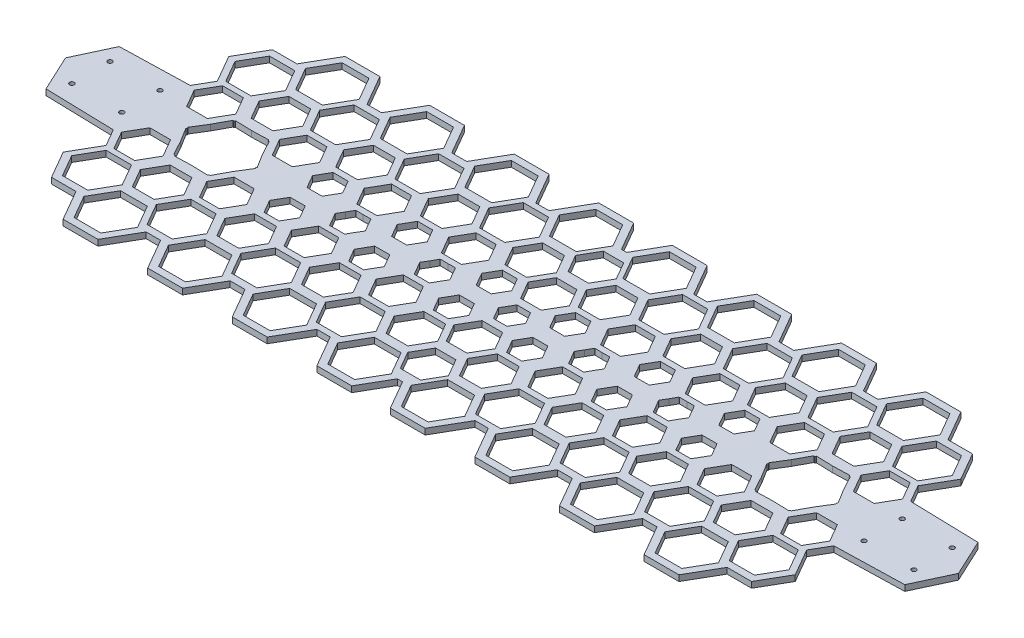
SolidWorks part; units mm, degrees
material "6061 Alloy"
ref_plane "Front Plane" through (0, 0, 0) normal (0, 0, 1) x (1, 0, 0)
ref_plane "Top Plane" through (0, 0, 0) normal (0, 1, 0) x (1, 0, 0)
ref_plane "Right Plane" through (0, 0, 0) normal (1, 0, 0) x (0, 0, -1)
sketch "Sketch2" plane through (0, 0, 0) normal (0, 1, 0) x (1, 0, 0)
  line L1 (-482.6, -152.4) -> (482.6, -152.4)
  line L2 (-482.6, -152.4) -> (-482.6, 152.4)
  line L3 (-482.6, 152.4) -> (482.6, 152.4)
  line L4 (482.6, -152.4) -> (482.6, 152.4)
  line L5 (-482.6, -152.4) -> (482.6, 152.4) construction
  line L6 (-482.6, 152.4) -> (482.6, -152.4) construction
  point P0 (0, 0)
  dimension "D1" = 304.8
  dimension "D2" = 965.2
extrude "Boss-Extrude1" add sketch "Sketch2" along normal blind 6.35
sketch "Sketch7" plane through (0, 6.35, 0) normal (0, 1, 0) x (1, 0, 0)
  line L166 (0, 0) -> (-401.7449, 0) construction
  line L215 (-31.5577, 37.3042) -> (-47.8332, 37.3042)
  line L216 (-47.8332, 37.3042) -> (-55.9709, 23.2093)
  line L217 (-55.9709, 23.2093) -> (-47.8332, 9.1144)
  line L218 (-47.8332, 9.1144) -> (-31.5577, 9.1144)
  line L219 (-31.5577, 9.1144) -> (-23.42, 23.2093)
  line L220 (-23.42, 23.2093) -> (-31.5577, 37.3042)
  line L221 (-16.1001, 64.2057) -> (-27.8978, 84.6399)
  line L222 (-27.8978, 84.6399) -> (-51.4931, 84.6399)
  line L223 (-51.4931, 84.6399) -> (-63.2908, 64.2057)
  line L224 (-63.2908, 64.2057) -> (-51.4931, 43.7716)
  line L225 (-51.4931, 43.7716) -> (-27.8978, 43.7716)
  line L226 (-27.8978, 43.7716) -> (-16.1001, 64.2057)
  line L227 (-10.6981, 119.7777) -> (-25.1968, 144.8901)
  line L228 (-25.1968, 144.8901) -> (-54.1941, 144.8901)
  line L229 (-54.1941, 144.8901) -> (-68.6928, 119.7777)
  line L230 (-68.6928, 119.7777) -> (-54.1941, 94.6652)
  line L231 (-54.1941, 94.6652) -> (-25.1968, 94.6652)
  line L232 (-25.1968, 94.6652) -> (-10.6981, 119.7777)
  line L233 (-64.4077, 39.3283) -> (-75.2304, 58.0738)
  line L234 (-75.2304, 58.0738) -> (-96.8759, 58.0738)
  line L235 (-96.8759, 58.0738) -> (-107.6986, 39.3283)
  line L236 (-107.6986, 39.3283) -> (-96.8759, 20.5828)
  line L237 (-96.8759, 20.5828) -> (-75.2304, 20.5828)
  line L238 (-75.2304, 20.5828) -> (-64.4077, 39.3283)
  line L239 (-58.7454, 88.2604) -> (-72.3993, 111.9096)
  line L240 (-72.3993, 111.9096) -> (-99.707, 111.9096)
  line L241 (-99.707, 111.9096) -> (-113.3609, 88.2604)
  line L242 (-113.3609, 88.2604) -> (-99.707, 64.6112)
  line L243 (-99.707, 64.6112) -> (-72.3993, 64.6112)
  line L244 (-72.3993, 64.6112) -> (-58.7454, 88.2604)
  line L245 (-122.9977, 37.3042) -> (-139.2732, 37.3042)
  line L246 (-67.2122, 0.2372) -> (-75.5284, 14.1669)
  line L247 (-75.5284, 14.1669) -> (-91.7499, 13.9297)
  line L248 (-91.7499, 13.9297) -> (-99.6553, -0.2372)
  line L249 (-99.6553, -0.2372) -> (-91.3391, -14.1669)
  line L250 (-91.3391, -14.1669) -> (-75.1176, -13.9297)
  line L251 (-75.1176, -13.9297) -> (-67.2122, 0.2372)
  line L252 (-139.2732, 37.3042) -> (-147.4109, 23.2093)
  line L253 (-147.4109, 23.2093) -> (-139.2732, 9.1144)
  line L254 (-139.2732, 9.1144) -> (-122.9977, 9.1144)
  line L255 (-122.9977, 9.1144) -> (-114.86, 23.2093)
  line L256 (-114.86, 23.2093) -> (-122.9977, 37.3042)
  line L257 (-107.5401, 64.2057) -> (-119.3378, 84.6399)
  line L258 (-119.3378, 84.6399) -> (-142.9331, 84.6399)
  line L259 (-142.9331, 84.6399) -> (-154.7308, 64.2057)
  line L260 (-154.7308, 64.2057) -> (-142.9331, 43.7716)
  line L261 (-142.9331, 43.7716) -> (-119.3378, 43.7716)
  line L262 (-119.3378, 43.7716) -> (-107.5401, 64.2057)
  line L263 (-102.1381, 119.7777) -> (-116.6368, 144.8901)
  line L264 (-116.6368, 144.8901) -> (-145.6341, 144.8901)
  line L265 (-145.6341, 144.8901) -> (-160.1328, 119.7777)
  line L266 (-160.1328, 119.7777) -> (-145.6341, 94.6652)
  line L267 (-145.6341, 94.6652) -> (-116.6368, 94.6652)
  line L268 (-116.6368, 94.6652) -> (-102.1381, 119.7777)
  line L269 (-155.8477, 39.3283) -> (-166.6704, 58.0738)
  line L270 (-166.6704, 58.0738) -> (-188.3159, 58.0738)
  line L271 (-188.3159, 58.0738) -> (-199.1386, 39.3283)
  line L272 (-199.1386, 39.3283) -> (-188.3159, 20.5828)
  line L273 (-188.3159, 20.5828) -> (-166.6704, 20.5828)
  line L274 (-166.6704, 20.5828) -> (-155.8477, 39.3283)
  line L275 (-150.1854, 88.2604) -> (-163.8393, 111.9096)
  line L276 (-163.8393, 111.9096) -> (-191.147, 111.9096)
  line L277 (-191.147, 111.9096) -> (-204.8009, 88.2604)
  line L278 (-204.8009, 88.2604) -> (-191.147, 64.6112)
  line L279 (-191.147, 64.6112) -> (-163.8393, 64.6112)
  line L280 (-163.8393, 64.6112) -> (-150.1854, 88.2604)
  line L281 (-158.6522, 0.2372) -> (-166.9684, 14.1669)
  line L282 (-166.9684, 14.1669) -> (-183.1899, 13.9297)
  line L283 (-183.1899, 13.9297) -> (-191.0953, -0.2372)
  line L284 (-191.0953, -0.2372) -> (-182.7791, -14.1669)
  line L285 (-182.7791, -14.1669) -> (-166.5576, -13.9297)
  line L286 (-166.5576, -13.9297) -> (-158.6522, 0.2372)
  line L287 (-214.4377, 37.3042) -> (-230.7132, 37.3042)
  line L288 (-230.7132, 37.3042) -> (-238.8509, 23.2093)
  line L289 (-238.8509, 23.2093) -> (-230.7132, 9.1144)
  line L290 (-230.7132, 9.1144) -> (-214.4377, 9.1144)
  line L291 (-214.4377, 9.1144) -> (-206.3, 23.2093)
  line L292 (-206.3, 23.2093) -> (-214.4377, 37.3042)
  line L293 (-198.9801, 64.2057) -> (-210.7778, 84.6399)
  line L294 (-210.7778, 84.6399) -> (-234.3731, 84.6399)
  line L295 (-234.3731, 84.6399) -> (-246.1708, 64.2057)
  line L296 (-246.1708, 64.2057) -> (-234.3731, 43.7716)
  line L297 (-234.3731, 43.7716) -> (-210.7778, 43.7716)
  line L298 (-210.7778, 43.7716) -> (-198.9801, 64.2057)
  line L299 (-193.5781, 119.7777) -> (-208.0768, 144.8901)
  line L300 (-208.0768, 144.8901) -> (-237.0741, 144.8901)
  line L301 (-237.0741, 144.8901) -> (-251.5728, 119.7777)
  line L302 (-251.5728, 119.7777) -> (-237.0741, 94.6652)
  line L303 (-237.0741, 94.6652) -> (-208.0768, 94.6652)
  line L304 (-208.0768, 94.6652) -> (-193.5781, 119.7777)
  line L305 (-247.2877, 39.3283) -> (-258.1104, 58.0738)
  line L306 (-258.1104, 58.0738) -> (-279.7559, 58.0738)
  line L307 (-279.7559, 58.0738) -> (-290.5786, 39.3283)
  line L308 (-290.5786, 39.3283) -> (-279.7559, 20.5828)
  line L309 (-279.7559, 20.5828) -> (-258.1104, 20.5828)
  line L310 (-258.1104, 20.5828) -> (-247.2877, 39.3283)
  line L311 (-241.6254, 88.2604) -> (-255.2793, 111.9096)
  line L312 (-255.2793, 111.9096) -> (-282.587, 111.9096)
  line L313 (-282.587, 111.9096) -> (-296.2409, 88.2604)
  line L314 (-296.2409, 88.2604) -> (-282.587, 64.6112)
  line L315 (-282.587, 64.6112) -> (-255.2793, 64.6112)
  line L316 (-255.2793, 64.6112) -> (-241.6254, 88.2604)
  line L329 (-290.4201, 64.2057) -> (-302.2178, 84.6399)
  line L330 (-302.2178, 84.6399) -> (-325.8131, 84.6399)
  line L331 (-325.8131, 84.6399) -> (-337.6108, 64.2057)
  line L332 (-337.6108, 64.2057) -> (-325.8131, 43.7716)
  line L333 (-325.8131, 43.7716) -> (-302.2178, 43.7716)
  line L334 (-302.2178, 43.7716) -> (-290.4201, 64.2057)
  line L335 (-285.0181, 119.7777) -> (-299.5168, 144.8901)
  line L336 (-299.5168, 144.8901) -> (-328.5141, 144.8901)
  line L337 (-328.5141, 144.8901) -> (-343.0128, 119.7777)
  line L338 (-343.0128, 119.7777) -> (-328.5141, 94.6652)
  line L339 (-328.5141, 94.6652) -> (-299.5168, 94.6652)
  line L340 (-299.5168, 94.6652) -> (-285.0181, 119.7777)
  line L347 (-333.0654, 88.2604) -> (-346.7193, 111.9096)
  line L348 (-346.7193, 111.9096) -> (-374.027, 111.9096)
  line L349 (-374.027, 111.9096) -> (-387.6809, 88.2604)
  line L350 (-387.6809, 88.2604) -> (-374.027, 64.6112)
  line L351 (-374.027, 64.6112) -> (-346.7193, 64.6112)
  line L352 (-346.7193, 64.6112) -> (-333.0654, 88.2604)
  line L359 (-338.7277, 39.3283) -> (-349.5504, 58.0738) [skipped]
  line L360 (-349.5504, 58.0738) -> (-371.1959, 58.0738) [skipped]
  line L361 (-371.1959, 58.0738) -> (-382.0186, 39.3283) [skipped]
  line L362 (-382.0186, 39.3283) -> (-371.1959, 20.5828) [skipped]
  line L363 (-371.1959, 20.5828) -> (-349.5504, 20.5828) [skipped]
  line L364 (-349.5504, 20.5828) -> (-338.7277, 39.3283) [skipped]
  line L365 (-341.5322, 0.2372) -> (-349.8484, 14.1669) [skipped]
  line L366 (-349.8484, 14.1669) -> (-366.0699, 13.9297) [skipped]
  line L367 (-366.0699, 13.9297) -> (-373.9753, -0.2372) [skipped]
  line L368 (-373.9753, -0.2372) -> (-365.6591, -14.1669) [skipped]
  line L369 (-365.6591, -14.1669) -> (-349.4376, -13.9297) [skipped]
  line L370 (-349.4376, -13.9297) -> (-341.5322, 0.2372) [skipped]
  line L371 (-305.8777, 37.3042) -> (-322.1532, 37.3042) [skipped]
  line L372 (-322.1532, 37.3042) -> (-330.2909, 23.2093) [skipped]
  line L373 (-330.2909, 23.2093) -> (-322.1532, 9.1144) [skipped]
  line L374 (-322.1532, 9.1144) -> (-305.8777, 9.1144) [skipped]
  line L375 (-305.8777, 9.1144) -> (-297.74, 23.2093) [skipped]
  line L376 (-297.74, 23.2093) -> (-305.8777, 37.3042) [skipped]
  line L384 (-250.0922, 0.2372) -> (-258.4084, 14.1669) [skipped]
  line L385 (-258.4084, 14.1669) -> (-274.6299, 13.9297) [skipped]
  line L386 (-274.6299, 13.9297) -> (-282.5353, -0.2372) [skipped]
  line L387 (-282.5353, -0.2372) -> (-274.2191, -14.1669) [skipped]
  line L388 (-257.9976, -13.9297) -> (-250.0922, 0.2372) [skipped]
  line L389 (-274.2191, -14.1669) -> (-257.9976, -13.9297) [skipped]
  line L390 (-296.2409, 33.0301) -> (-333.7331, 31.9082)
  line L391 (-333.7331, 31.9082) -> (-351.5076, -1.1218)
  line L392 (-351.5076, -1.1218) -> (-331.79, -33.0301)
  line L393 (-331.79, -33.0301) -> (-294.2978, -31.9082)
  line L394 (-294.2978, -31.9082) -> (-276.5233, 1.1218)
  line L395 (-276.5233, 1.1218) -> (-296.2409, 33.0301)
  line L396 (-337.9205, 39.3283) -> (-349.1468, 58.7729)
  line L397 (-349.1468, 58.7729) -> (-371.5995, 58.7729)
  line L398 (-371.5995, 58.7729) -> (-382.8259, 39.3283)
  line L399 (-382.8259, 39.3283) -> (-371.5995, 19.8837)
  line L400 (-371.5995, 19.8837) -> (-349.1468, 19.8837)
  line L401 (-349.1468, 19.8837) -> (-337.9205, 39.3283)
  circle A1 centre (-39.6954, 23.2093) radius 14.0949 construction
  circle A2 centre (-39.6954, 64.2057) radius 20.4341 construction
  circle A3 centre (-39.6954, 119.7777) radius 25.1125 construction
  circle A4 centre (-86.0532, 39.3283) radius 18.7455 construction
  circle A5 centre (-86.0532, 88.2604) radius 23.6492 construction
  circle A6 centre (-83.4337, 0) radius 14.0498 construction
  circle A7 centre (-131.1354, 23.2093) radius 14.0949 construction
  circle A8 centre (-131.1354, 64.2057) radius 20.4341 construction
  circle A9 centre (-131.1354, 119.7777) radius 25.1125 construction
  circle A10 centre (-177.4932, 39.3283) radius 18.7455 construction
  circle A11 centre (-177.4932, 88.2604) radius 23.6492 construction
  circle A12 centre (-174.8737, 0) radius 14.0498 construction
  circle A13 centre (-222.5754, 23.2093) radius 14.0949 construction
  circle A14 centre (-222.5754, 64.2057) radius 20.4341 construction
  circle A15 centre (-222.5754, 119.7777) radius 25.1125 construction
  circle A16 centre (-268.9332, 39.3283) radius 18.7455 construction
  circle A17 centre (-268.9332, 88.2604) radius 23.6492 construction
  circle A18 centre (-314.0154, 0) radius 32.4837 construction
  circle A19 centre (-360.3732, 39.3283) radius 19.4446 construction
  circle A20 centre (-314.0154, 64.2057) radius 20.4341 construction
  circle A21 centre (-314.0154, 119.7777) radius 25.1125 construction
  circle A23 centre (-360.3732, 88.2604) radius 23.6492 construction
  circle A25 centre (-360.3732, 39.3283) radius 18.7455 construction
  circle A26 centre (-357.7537, 0) radius 14.0498 construction
  circle A27 centre (-314.0154, 23.2093) radius 14.0949 construction
  circle A28 centre (-266.3137, 0) radius 14.0498 construction
  dimension "D1" = 2
  dimension "D2" = 2
extrude "Cut-Extrude3" cut sketch "Sketch7" against normal through all
sketch "Sketch3" plane through (0, 6.35, 0) normal (0, 1, 0) x (1, 0, 0)
  line L0 (0, 0) -> (-890.435, 0) construction
  line L1 (0, 0) -> (901.0118, 0) construction
  line L2 (0, 0) -> (0, 150.6469) construction
  line L3 (0, 0) -> (0, -245.2497) construction
  line L4 (-482.6, 0) -> (-464.1422, 39.5829)
  line L9 (-20.8609, 152.4) -> (-2.8236, 121.1584)
  line L16 (-482.6, 0) -> (-689.3836, 0)
  line L17 (-689.3836, 0) -> (-689.3836, 240.3533)
  line L18 (-689.3836, 240.3533) -> (-11.7344, 240.3533)
  line L20 (-482.6, 152.4) -> (-482.6, -152.4) construction
  line L22 (482.6, 152.4) -> (-482.6, 152.4) construction
  line L23 (-20.8609, 152.4) -> (-58.53, 152.4)
  line L24 (-58.53, 152.4) -> (-78.2518, 118.2408)
  line L25 (-78.2518, 118.2408) -> (-92.5791, 118.2408)
  line L26 (-92.5791, 118.2408) -> (-112.3009, 152.4)
  line L27 (-112.3009, 152.4) -> (-149.97, 152.4)
  line L28 (-149.97, 152.4) -> (-168.8045, 119.7777)
  line L29 (-168.8045, 119.7777) -> (-184.9064, 119.7777)
  line L30 (-184.9064, 119.7777) -> (-203.7409, 152.4)
  line L31 (-203.7409, 152.4) -> (-241.41, 152.4)
  line L32 (-241.41, 152.4) -> (-260.4513, 119.4194)
  line L33 (-260.4513, 119.4194) -> (-276.1396, 119.4194)
  line L34 (-276.1396, 119.4194) -> (-295.1809, 152.4)
  line L35 (-295.1809, 152.4) -> (-332.85, 152.4)
  line L36 (-332.85, 152.4) -> (-351.8913, 119.4194)
  line L37 (-351.8913, 119.4194) -> (-378.3629, 119.4194)
  line L38 (-378.3629, 119.4194) -> (-395.6522, 89.4735)
  line L39 (-328.5141, 144.8901) -> (-343.0128, 119.7777) construction
  line L40 (-374.027, 111.9096) -> (-387.6809, 88.2604) construction
  line L41 (-395.6522, 89.4735) -> (-378.6955, 60.1038)
  line L42 (-378.6955, 60.1038) -> (-389.4003, 41.5626)
  line L43 (-389.4003, 41.5626) -> (-464.1422, 39.5829)
  line L44 (-387.6809, 88.2604) -> (-374.027, 64.6112) construction
  line L45 (-378.7378, 103.7502) -> (-385.2416, 107.5052) construction
  line L46 (-381.5581, 55.1457) -> (-375.0544, 51.3907) construction
  line L47 (-2.8236, 121.1584) -> (0, 121.1584)
  line L48 (-10.6981, 119.7777) -> (-25.1968, 144.8901) construction
  line L49 (-102.1381, 119.7777) -> (-116.6368, 144.8901) construction
  line L50 (-54.1941, 144.8901) -> (-68.6928, 119.7777) construction
  line L51 (-72.3993, 111.9096) -> (-99.707, 111.9096) construction
  line L52 (-193.5781, 119.7777) -> (-208.0768, 144.8901) construction
  line L53 (-163.8393, 111.9096) -> (-191.147, 111.9096) construction
  line L54 (-145.6341, 144.8901) -> (-160.1328, 119.7777) construction
  line L56 (-25.1968, 144.8901) -> (-54.1941, 144.8901) construction
  line L57 (-39.6954, 144.8901) -> (-39.6954, 152.4) construction
  line L58 (-85.4154, 110.7309) -> (-85.4154, 118.2408) construction
  line L59 (-100.8822, 132.6222) -> (-107.3859, 128.8673) construction
  line L60 (-160.0362, 134.9647) -> (-153.5325, 131.2098) construction
  line L61 (-176.8554, 112.2678) -> (-176.8554, 119.7777) construction
  line L62 (-200.8274, 132.3339) -> (-194.3237, 136.0888) construction
  line L63 (-244.3235, 132.3339) -> (-250.8272, 136.0888) construction
  line L64 (-237.0741, 144.8901) -> (-251.5728, 119.7777) construction
  line L65 (-70.2675, 132.0699) -> (-63.7638, 128.315) construction
  line L66 (-264.0557, 111.9096) -> (-264.0557, 119.4194) construction
  line L67 (-255.2793, 111.9096) -> (-282.587, 111.9096) construction
  line L68 (-295.727, 138.326) -> (-289.2232, 142.0809) construction
  line L69 (-285.0181, 119.7777) -> (-299.5168, 144.8901) construction
  line L70 (-332.3039, 138.326) -> (-338.8077, 142.0809) construction
  line L71 (-346.7193, 111.9096) -> (-374.027, 111.9096) construction
  line L72 (-358.3286, 111.9096) -> (-358.3286, 119.4194) construction
  line L73 (-392.2503, 83.5814) -> (-386.7972, 86.7297) construction
  line L74 (-371.1959, 58.0738) -> (-382.0186, 39.3283) construction
  line L75 (0, 121.1584) -> (0, 240.3533)
  line L76 (0, 240.3533) -> (-11.7344, 240.3533)
  point P98 (-457.2, 0)
  dimension "D1" = 65
sketch "Sketch8" plane through (0, 6.35, 0) normal (0, 1, 0) x (1, 0, 0)
  line L0 (0, 0) -> (-25.8494, 0) construction
  line L1 (10.9945, 109.7378) -> (-10.9945, 109.7378)
  line L2 (-10.9945, 109.7378) -> (-21.989, 90.6948)
  line L3 (-21.989, 90.6948) -> (-10.9945, 71.6518)
  line L4 (-10.9945, 71.6518) -> (10.9945, 71.6518)
  line L5 (10.9945, 71.6518) -> (21.989, 90.6948)
  line L6 (21.989, 90.6948) -> (10.9945, 109.7378)
  line L7 (10.7289, 59.45) -> (-11.5565, 59.45)
  line L8 (-11.5565, 59.45) -> (-22.6991, 40.1504)
  line L9 (-22.6991, 40.1504) -> (-11.5565, 20.8507)
  line L10 (-11.5565, 20.8507) -> (10.7289, 20.8507)
  line L11 (10.7289, 20.8507) -> (21.8715, 40.1504)
  line L12 (21.8715, 40.1504) -> (10.7289, 59.45)
  line L13 (7.342, 12.7167) -> (-7.342, 12.7167)
  line L14 (-7.342, 12.7167) -> (-14.684, 0)
  line L15 (-14.684, 0) -> (-7.342, -12.7167)
  line L16 (-7.342, -12.7167) -> (7.342, -12.7167)
  line L17 (7.342, -12.7167) -> (14.684, 0)
  line L18 (14.684, 0) -> (7.342, 12.7167)
  circle A0 centre (0, 90.6948) radius 19.043 construction
  circle A1 centre (-0.4138, 40.1504) radius 19.2996 construction
  circle A2 centre (0, 0) radius 12.7167 construction
extrude "Cut-Extrude4" cut sketch "Sketch8" against normal through all
extrude "Cut-Extrude5" cut sketch "Sketch3" against normal through all
fillet "Fillet1" [suppressed] radius 2.38
mirror "Mirror10" about plane through (0, 0, 0) normal (1, 0, 0) of "Cut-Extrude5", "Cut-Extrude3"
mirror "Mirror11" about plane through (0, 0, 0) normal (0, 0, 1) of "Cut-Extrude4", "Mirror10"
hole_wizard "#10 (0.1935) Diameter Hole2" positions "Sketch11" profile "Sketch10" hole size "#10" standard "ANSI Inch" end condition through all
sketch "Sketch11" plane through (0, 6.35, 0) normal (0, 1, 0) x (1, 0, 0)
  line L0 (-455.1274, 0) -> (-455.1274, 20.6375) construction
  line L2 (-455.1274, 0) -> (-455.1274, -20.6375) construction
  line L4 (-455.1274, 20.6375) -> (-401.1524, 20.6375) construction
  line L6 (-401.1524, 20.6375) -> (-401.1524, -20.6375) construction
  point P2 (-455.1274, 20.6375)
  point P7 (-455.1274, -20.6375)
  point P12 (-401.1524, 20.6375)
  point P17 (-401.1524, -20.6375)
  dimension "D1" = 20.6375
  dimension "D2" = 20.6375
  dimension "D3" = 53.975
sketch "Sketch10" plane through (-401.1524, 6.35, 20.6375) normal (1, 0, 0) x (0, 0, 1)
  line L0 (0, 0) -> (0, 6.35)
  line L1 (0, 6.35) -> (2.4574, 6.35)
  line L2 (2.4574, 6.35) -> (2.4574, 0)
  line L5 (2.4574, 0) -> (0, 0)
  line L11 (0, -6.35) -> (0, 107.95) construction
  dimension "Thru Hole Dia." = 4.9149
  dimension "Thru Hole Depth" = 6.35
mirror "Mirror12" about plane through (0, 0, 0) normal (1, 0, 0) of "#10 (0.1935) Diameter Hole2"
